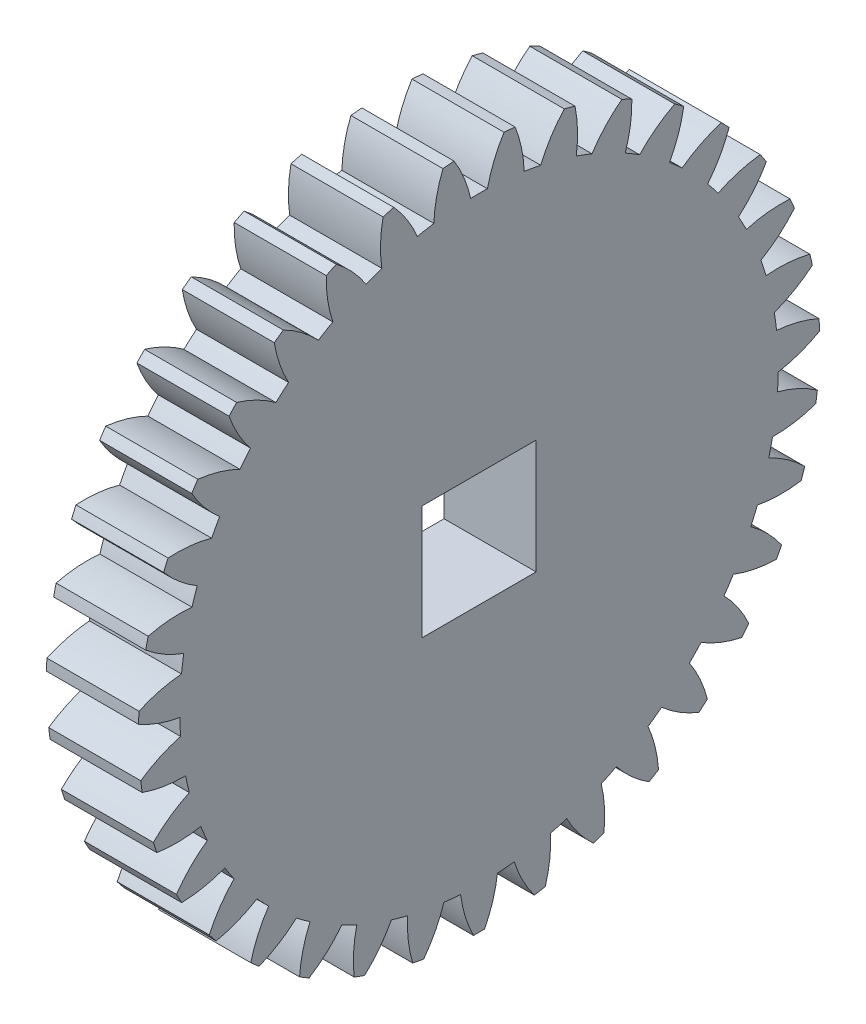
SolidWorks part; units mm, degrees
ref_plane "Plane1" through (0, 0, 0) normal (0, 0, 1) x (1, 0, 0)
ref_plane "Plane2" through (0, 0, 0) normal (0, 1, 0) x (1, 0, 0)
ref_plane "Plane3" through (0, 0, 0) normal (1, 0, 0) x (0, 0, -1)
sketch "HoldingSke" plane through (0, 0, 0) normal (0, 1, 0) x (1, 0, 0)
  line L0 (0, 0) -> (0.8192, -0.5736)
  line L1 (-15, 0) -> (100, 0) construction
  line L2 (0, 0) -> (-2.1039, 2.3779)
  line L3 (0, 0) -> (-11.863, 4.5341)
  line L4 (0, 0) -> (7.0742, 4.9534)
  line L5 (0, 0) -> (-46.8476, -17.4728)
  line L6 (0, 0) -> (-4.1448, -2.7965)
  line L7 (-2.1039, 2.3779) -> (8.6586, 51.2059)
  line L8 (-76.2, 54.61) -> (-75.2, 54.61)
  line L9 (-71.009, 38.7566) -> (-53.1078, 45.2721)
  line L10 (-76.2, 71.12) -> (104.1128, 71.12)
  line L11 (0, 0) -> (-5, 0)
  line L12 (-76.2, 101.6) -> (-76.162, 101.6)
  line L13 (24.9733, 27.94) -> (52.9518, 28.4284)
  line L14 (24.9733, 27.94) -> (24.9743, 27.94)
  line L15 (24.9733, 27.94) -> (100.4006, 29.5858)
  line L16 (-63.627, -1) -> (-12.827, -1)
  circle A0 centre (0, 0) radius 3
  circle A1 centre (0, 0) radius 16.249
  circle A2 centre (0, 0) radius 37.5
  circle A3 centre (0, 0) radius 3
  dimension "MHD" = 32.498
  dimension "Hub_dia" = 75
  dimension "Bore" = 6
  dimension "MBD" = 6
  dimension "Num_teeth" = 35
  dimension "Pitch_radius" = 180.3128
  dimension "Pitch" = 1
  dimension "Width" = 5
  dimension "Overall_len" = 50
  dimension "Show_teeth" = 35
  dimension "Thickness" = 5
  dimension "OAL" = 50.0001
  dimension "T_dim" = 1
  dimension "Ap" = 20
  dimension "H" = 19.05
  dimension "Backlash" = 0.038
  dimension "Addendum_fac" = 1
  dimension "Dedendum_fac" = 1.25
  dimension "Clearance_fac" = 0.25
  dimension "Dedendum_add" = 0.001
  dimension "Module" = 1
sketch "BasProSke" plane through (0, 0, 0) normal (0, 1, 0) x (1, 0, 0)
  line L0 (-10, 0) -> (60, 0) construction
  line L1 (0, 0) -> (0, 18.5)
  line L2 (0, 0) -> (5, 0)
  line L3 (5, 0) -> (5, 18.5)
  line L4 (5, 18.5) -> (0, 18.5)
  dimension "Diameter" = 37
  dimension "Thickness" = 5
revolve "Base-Revolve" add sketch "BasProSke" angle 360 about L0
sketch "TooCutSke" plane through (0, 0, 0) normal (1, 0, 0) x (0, 0, -1)
  line L1 (0, 0) -> (0, 107) construction
  line L2 (0, 0) -> (-0.8516, 17.4793) construction
  line L3 (0, 0) -> (-3.1347, 34.8297) construction
  line L4 (-0.8516, 17.4793) -> (-1.5674, 17.4148) construction
  arc A0 (0.4564, 16.2426) -> (-0.4564, 16.2426) centre (0, 0) ccw
  arc A1 (1.373, 18.4745) -> (-1.373, 18.4745) centre (0, 0) ccw
  circle A2 centre (0, 0) radius 17.5 construction
  circle A3 centre (0, 0) radius 16.4446 construction
  arc A4 (-0.4564, 16.2426) -> (-1.373, 18.4745) centre (-7.293, 14.739) ccw
  arc A5 (1.373, 18.4745) -> (0.4564, 16.2426) centre (7.293, 14.739) ccw
  dimension "Root_dia" = 32.498
  dimension "Overcut_dia" = 37.0508
  dimension "Pitch_dia" = 35
  dimension "Base_dia" = 32.8892
  dimension "Flank_rad" = 7
  dimension "Half_ang" = 5.143
  dimension "Half_CT" = 0.7186
extrude "ToothCut" cut sketch "TooCutSke" along normal through all
fillet "Breaks" [suppressed] radius 0.02 tangent propagation no
fillet "RootFillets" [suppressed] radius 0.251
pattern_circular "TeethCuts" count 35 every 10.286 about axis through (-10, 0, 0) along (1, 0, 0) of "ToothCut", "RootFillets", "Breaks"
sketch "HubNeaOneSke" plane through (0, 0, 0) normal (-1, 0, 0) x (0, 0, 1)
  circle A0 centre (0, 0) radius 16.249
  dimension "Diameter" = 32.498
extrude "HubNearOne" [suppressed] add sketch "HubNeaOneSke" along normal blind 45.0001
sketch "HubNeaBotSke" plane through (0, 0, 0) normal (-1, 0, 0) x (0, 0, 1)
  circle A0 centre (0, 0) radius 16.249
  dimension "Diameter" = 32.498
extrude "HubNearBoth" [suppressed] add sketch "HubNeaBotSke" along normal blind 22.5
ref_plane "FarPln" through (5, 0, 0) normal (1, 0, 0) x (0, 0, -1)
sketch "HubFarSke" plane through (5, 0, 0) normal (1, 0, 0) x (0, 0, -1)
  circle A0 centre (0, 0) radius 16.249
  dimension "Diameter" = 32.498
extrude "HubFar" [suppressed] add sketch "HubFarSke" along normal blind 22.5
sketch "BorSke" plane through (0, 0, 0) normal (1, 0, 0) x (0, 0, -1)
  circle A0 centre (0, 0) radius 1.5
  dimension "Diameter" = 3
extrude "Bore" cut sketch "BorSke" along normal mid plane 100.0001
sketch "KeySke" plane through (0, 0, 0) normal (1, 0, 0) x (0, 0, -1)
  line L0 (-1, 0) -> (-1, 4)
  line L1 (-1, 4) -> (1, 4)
  line L2 (1, 4) -> (1, 0)
  line L3 (0, 0) -> (0, 34) construction
  line L4 (-1, 0) -> (1, 0)
  dimension "Offset" = 4
  dimension "Width" = 2
extrude "Keyway" [suppressed] cut sketch "KeySke" along normal mid plane 100.0001
pattern_circular "Keyway2" [suppressed] count 2 every 90 about axis through (-10, 0, 0) along (1, 0, 0)
sketch "Sketch1" plane through (5, 0, 0) normal (1, 0, 0) x (0, 0, -1)
  line L1 (-3.1, -3.1) -> (3.1, -3.1)
  line L2 (-3.1, -3.1) -> (-3.1, 3.1)
  line L3 (-3.1, 3.1) -> (3.1, 3.1)
  line L4 (3.1, -3.1) -> (3.1, 3.1)
  line L5 (-3.1, -3.1) -> (3.1, 3.1) construction
  line L6 (-3.1, 3.1) -> (3.1, -3.1) construction
  circle A0 centre (0, 0) radius 1.5 construction
  point P0 (0, 0)
  dimension "D1" = 0
  dimension "D2" = 6.2
  dimension "D3" = 6.2
extrude "Cut-Extrude1" cut sketch "Sketch1" against normal blind 10
equation "' \"Module@HoldingSke\" = 6.35"
equation "' \"Num_teeth@HoldingSke\" = 12"
equation "' \"Ap@HoldingSke\" =  20"
equation "' \"Width@HoldingSke\" = 0.5 * 25.4"
equation "' \"Hub_dia@HoldingSke\"= 1 * 25.4"
equation "' \"Overall_len@HoldingSke\" = 1.0 * 25.4"
equation "' \"Bore@HoldingSke\" = 0.75 * 25.4"
equation "' \"T_dim@HoldingSke\" = 0.1 * 25.4"
equation "' \"Width@KeySke\" = 0.25 * 25.4"
equation "' \"Show_teeth@HoldingSke\" = 13"
equation "' \"Backlash@HoldingSke\" = 0.009 * 25.4"
equation "' \"Addendum_fac@HoldingSke\" = 1.0"
equation "' \"Dedendum_fac@HoldingSke\" = 1.25"
equation "' \"Dedendum_add@HoldingSke\" = 0.00005 * 25.4"
equation "' \"Clearance_fac@HoldingSke\" = 0.25"
equation "\"Pitch@HoldingSke\" = 1 / \"Module@HoldingSke\""
equation "\"Overcut_dia@TooCutSke\" = (\"Num_teeth@HoldingSke\" + 2 * \"Addendum_fac@HoldingSke\") / \"Pitch@HoldingSke\" + 0.002 * 25.4"
equation "\"Pitch_dia@TooCutSke\" = \"Num_teeth@HoldingSke\" / \"Pitch@HoldingSke\""
equation "\"Base_dia@TooCutSke\" = \"Num_teeth@HoldingSke\" / \"Pitch@HoldingSke\" * cos((\"Ap@HoldingSke\"  * 3.14159265 / 180))"
equation "\"Root_dia@TooCutSke\" = (\"Num_teeth@HoldingSke\" + 2) / \"Pitch@HoldingSke\" - 2 * (\"Addendum_fac@HoldingSke\" + \"Dedendum_fac@HoldingSke\") / \"Pitch@HoldingSke\" - \"Dedendum_add@HoldingSke\" * 2"
equation "\"Half_ang@TooCutSke\" = 180 / \"Num_teeth@HoldingSke\""
equation "\"Half_CT@TooCutSke\" = \"Num_teeth@HoldingSke\" / \"Pitch@HoldingSke\" * sin((3.14159265 / 2 / \"Num_teeth@HoldingSke\")) / 2 - 7 * \"Backlash@HoldingSke\" / 4"
equation "\"Flank_rad@TooCutSke\" = \"Num_teeth@HoldingSke\" / \"Pitch@HoldingSke\" / 5"
equation "\"Radius@RootFillets\" = \"Clearance_fac@HoldingSke\" / \"Pitch@HoldingSke\" + \"Dedendum_add@HoldingSke\""
equation "\"Break_rad@Breaks\" = 0.02 / \"Pitch@HoldingSke\""
equation "\"Thickness@HoldingSke\" = \"Width@HoldingSke\""
equation "\"OAL@HoldingSke\" = \"Thickness@HoldingSke\""
equation "\"MHD@HoldingSke\" = (\"Num_teeth@HoldingSke\" + 2) / \"Pitch@HoldingSke\" - 2 * (\"Addendum_fac@HoldingSke\" + \"Dedendum_fac@HoldingSke\")  / \"Pitch@HoldingSke\" - \"Dedendum_add@HoldingSke\" * 2"
equation "\"MBD@HoldingSke\" = (\"Num_teeth@HoldingSke\" + 2) / \"Pitch@HoldingSke\" - 2 * (\"Addendum_fac@HoldingSke\" + \"Dedendum_fac@HoldingSke\")  / \"Pitch@HoldingSke\" - \"Dedendum_add@HoldingSke\" * 2 - 0.002 * 25.4"
equation "\"MHD@HoldingSke\" = ((sgn( \"MHD@HoldingSke\" - \"Hub_dia@HoldingSke\" )-1)*( \"MHD@HoldingSke\" - \"Hub_dia@HoldingSke\" ))/-2+ \"Hub_dia@HoldingSke\""
equation "\"MBD@HoldingSke\" = ((sgn( \"MBD@HoldingSke\" - \"Bore@HoldingSke\" )-1)*( \"MBD@HoldingSke\" - \"Bore@HoldingSke\" ))/-2+ \"Bore@HoldingSke\""
equation "\"OAL@HoldingSke\" = ((sgn( \"OAL@HoldingSke\" - \"Overall_len@HoldingSke\" )+1)*( \"OAL@HoldingSke\" - \"Overall_len@HoldingSke\" ))/2 + \"Overall_len@HoldingSke\" + 0.000002 * 25.4"
equation "\"Num_teeth@TeethCuts\" = int( \"Show_teeth@HoldingSke\" ) + 1"
equation "\"Num_teeth@TeethCuts\" = ((sgn( \"Num_teeth@TeethCuts\" - \"Num_teeth@HoldingSke\" )-1)*( \"Num_teeth@TeethCuts\" - \"Num_teeth@HoldingSke\" ))/-2+ \"Num_teeth@HoldingSke\""
equation "\"Num_teeth@TeethCuts\" = ((sgn( \"Num_teeth@TeethCuts\" - 2.0)+1)*( \"Num_teeth@TeethCuts\" - 2.0))/2 +2.0"
equation "\"Angle@TeethCuts\" = 360.0 / \"Num_teeth@HoldingSke\""
equation "\"Diameter@BasProSke\" = (\"Num_teeth@HoldingSke\" + 2 * \"Addendum_fac@HoldingSke\") / \"Pitch@HoldingSke\""
equation "\"Thickness@BasProSke\"  = \"Thickness@HoldingSke\""
equation "' \"Fillet_rad@BasProSke\" =  \"Thickness@HoldingSke\" * 0.05"
equation "\"MHD@HoldingSke\" = ((sgn( \"MHD@HoldingSke\" - \"Root_dia@TooCutSke\" )-1)*( \"MHD@HoldingSke\" - \"Root_dia@TooCutSke\" ))/-2+ \"Root_dia@TooCutSke\""
equation "\"Diameter@HubNeaOneSke\" = \"MHD@HoldingSke\""
equation "\"Length@HubNearOne\" = \"OAL@HoldingSke\" - \"Thickness@BasProSke\""
equation "\"Diameter@HubNeaBotSke\" = \"MHD@HoldingSke\""
equation "\"Length@HubNearBoth\" = ( \"OAL@HoldingSke\" - \"Thickness@BasProSke\" ) / 2.0"
equation "\"Thickness@FarPln\" = \"Thickness@BasProSke\""
equation "\"Diameter@HubFarSke\" = \"MHD@HoldingSke\""
equation "\"Length@HubFar\" = ( \"OAL@HoldingSke\" - \"Thickness@BasProSke\" ) / 2.0"
equation "\"Diameter@BorSke\"=3"
equation "\"D1@Bore\" = \"OAL@HoldingSke\" * 2.0"
equation "\"D1@Keyway\" = \"OAL@HoldingSke\" * 2.0"
equation "\"Offset@KeySke\" = \"T_dim@HoldingSke\" + \"MBD@HoldingSke\" / 2.0"
